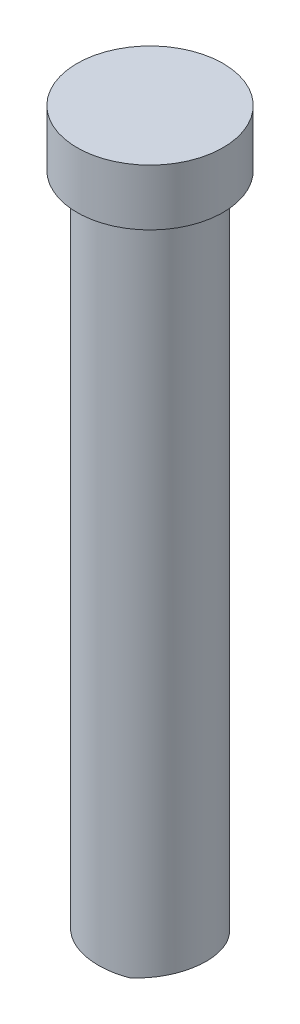
SolidWorks part; units mm, degrees
material "M2 HSS"
ref_plane "Front Plane" through (0, 0, 0) normal (0, 0, 1) x (1, 0, 0)
ref_plane "Top Plane" through (0, 0, 0) normal (0, 1, 0) x (1, 0, 0)
ref_plane "Right Plane" through (0, 0, 0) normal (1, 0, 0) x (0, 0, -1)
sketch "Sketch1" plane through (0, 0, 0) normal (0, 0, 1) x (1, 0, 0)
  line L0 (0, 0) -> (6.5, 0)
  line L1 (6.5, 0) -> (6.5, -5)
  line L2 (6.5, -5) -> (5, -5)
  line L3 (5, -5) -> (5, -64.2)
  line L4 (5, -64.2) -> (0, -64.2)
  line L5 (0, -64.2) -> (0, 0)
  line L6 (0, -69.2) -> (0, 5) construction
  dimension "D1" = 5
  dimension "D2" = 64.2
  dimension "D3" = 5
  dimension "D4" = 5
  dimension "D5" = 10
  dimension "D6" = 13
revolve "Revolve1" add sketch "Sketch1" angle 360 about L6
sketch "Sketch2" plane through (0, 0, 0) normal (0, 0, 1) x (1, 0, 0)
  line L0 (0, -64.2) -> (5, -63.4973)
  line L1 (-5, -64.2) -> (5, -64.2) construction
  line L2 (5, -64.2) -> (5, -5) construction
  line L3 (5, -63.4973) -> (5, -64.2)
  line L4 (5, -64.2) -> (0, -64.2)
  dimension "D1" = 5
  dimension "D2" = 8
  dimension "D3" = 0.7027
extrude "Cut-Extrude1" cut sketch "Sketch2" against normal through all both and the other way through all
pattern_circular "CirPattern1" count 3 over 360 about axis through (0, -64.2, 0) along (0, -1, 0) of "Cut-Extrude1"
